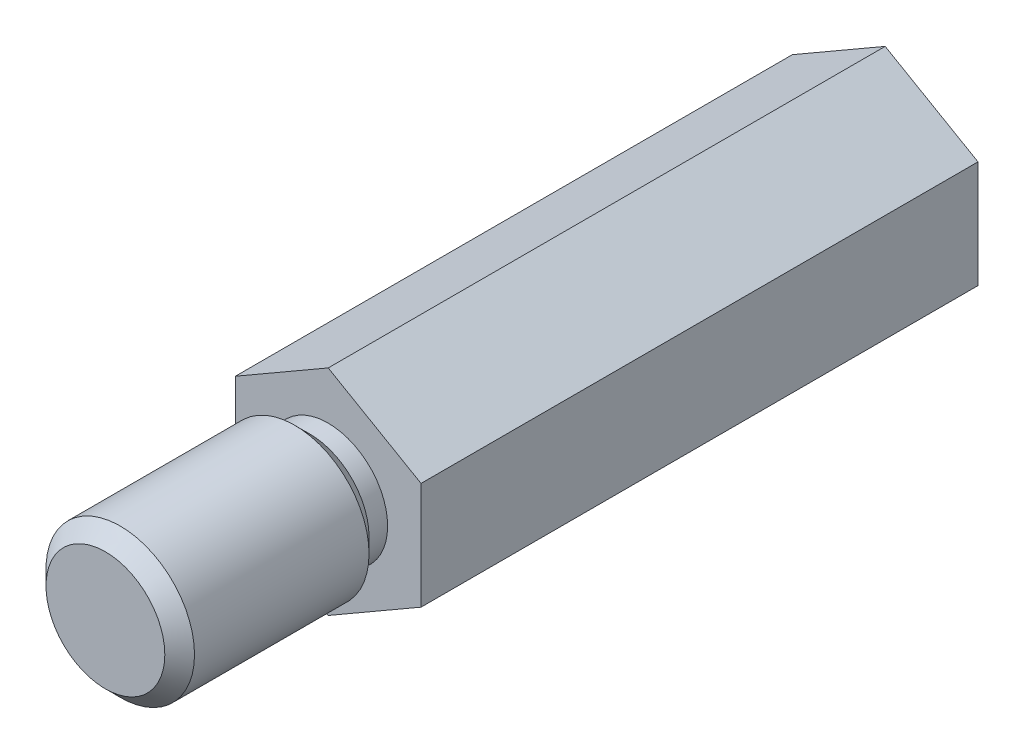
SolidWorks part; units mm, degrees
ref_plane "Спереди" through (0, 0, 0) normal (0, 0, 1) x (1, 0, 0)
ref_plane "Сверху" through (0, 0, 0) normal (0, 1, 0) x (1, 0, 0)
ref_plane "Справа" through (0, 0, 0) normal (1, 0, 0) x (0, 0, -1)
sketch "Эскиз1" plane through (0, 0, 0) normal (0, 0, 1) x (1, 0, 0)
  line L1 (0, 2.8868) -> (-2.5, 1.4434)
  line L2 (-2.5, 1.4434) -> (-2.5, -1.4434)
  line L3 (-2.5, -1.4434) -> (0, -2.8868)
  line L4 (0, -2.8868) -> (2.5, -1.4434)
  line L5 (2.5, -1.4434) -> (2.5, 1.4434)
  line L6 (2.5, 1.4434) -> (0, 2.8868)
  circle A0 centre (0, 0) radius 2.5 construction
  dimension "D1" = 5
extrude "Вытянуть1" add sketch "Эскиз1" along normal blind 15
sketch "Эскиз2" plane through (0, 0, 15) normal (0, 0, 1) x (1, 0, 0)
  circle A0 centre (0, 0) radius 2
  dimension "D1" = 4
extrude "Вытянуть2" add sketch "Эскиз2" along normal blind 6
cosmetic thread "Условное изображение резьбы1" parameters "D2"=3.4
sketch "Эскиз3" plane through (0, 0, 15) normal (0, 0, 1) x (1, 0, 0)
  circle A0 centre (0, 0) radius 1.6
  circle A1 centre (0, 0) radius 2 construction
  circle A2 centre (0, 0) radius 2
  dimension "D1" = 3.2
extrude "Вырез-Вытянуть3" cut sketch "Эскиз3" along normal blind 0.5
chamfer "Фаска1" distance 0.4 angle 45 2 edges at (2, 0, 15.5) (2, 0, 21)
